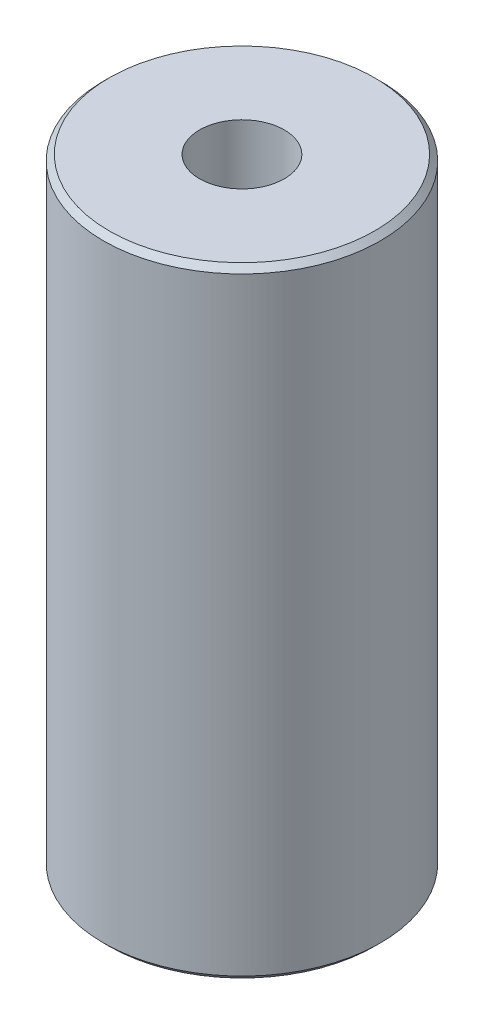
SolidWorks part; units mm, degrees
ref_plane "Front Plane" through (0, 0, 0) normal (0, 0, 1) x (1, 0, 0)
ref_plane "Top Plane" through (0, 0, 0) normal (0, 1, 0) x (1, 0, 0)
ref_plane "Right Plane" through (0, 0, 0) normal (1, 0, 0) x (0, 0, -1)
sketch "Sketch1" plane through (0, 0, 0) normal (0, 1, 0) x (1, 0, 0)
  circle A0 centre (0, 0) radius 32.5
  dimension "SHAFT_OD" = 65
extrude "Boss-Extrude1" add sketch "Sketch1" along normal blind 145.4365
sketch "Sketch2" plane through (0, 0, 0) normal (0, 1, 0) x (1, 0, 0)
  circle A0 centre (0, 0) radius 9.9535
  dimension "BORE_D" = 19.9069
extrude "Cut-Extrude1" cut sketch "Sketch2" along normal through all
chamfer "Chamfer1" distance 1.3474 angle 45 2 edges at (0, 145.4365, 32.5) (0, 0, 32.5)
